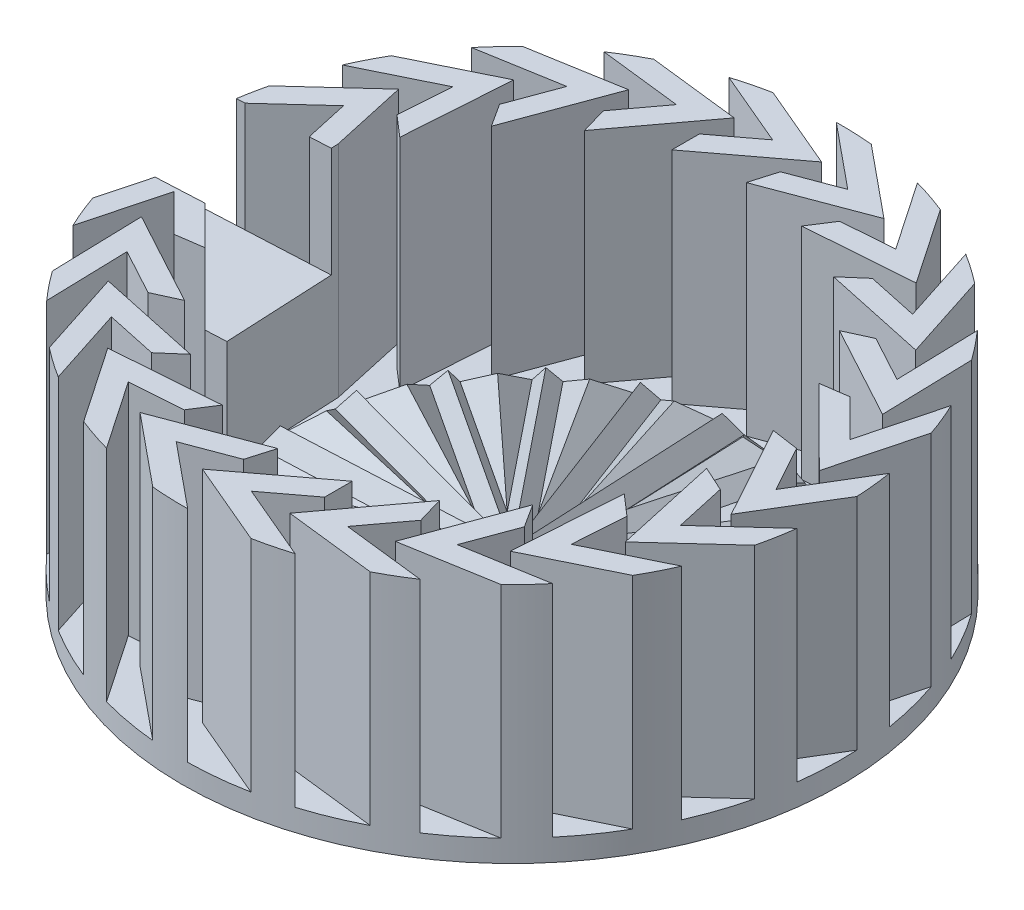
SolidWorks part; units mm, degrees
ref_plane "Front Plane" through (0, 0, 0) normal (0, 0, 1) x (1, 0, 0)
ref_plane "Top Plane" through (0, 0, 0) normal (0, 1, 0) x (1, 0, 0)
ref_plane "Right Plane" through (0, 0, 0) normal (1, 0, 0) x (0, 0, -1)
sketch "Sketch2" plane through (0, 0, 0) normal (0, 1, 0) x (1, 0, 0)
  circle A0 centre (0, 0) radius 30
  dimension "D1" = 60
extrude "Boss-Extrude1" add sketch "Sketch2" along normal blind 2
sketch "Sketch3" plane through (0, 2, 0) normal (0, 1, 0) x (1, 0, 0)
  line L0 (0, 0) -> (0, 30) construction
  line L1 (-7.364, 29.0821) -> (0, 25.9563) construction
  line L2 (0, 25.9563) -> (-6.3891, 21.1418) construction
  line L3 (-7.7548, 28.1616) -> (-1.9851, 25.7126) construction
  line L4 (-1.9851, 25.7126) -> (-6.9909, 21.9404) construction
  line L5 (-6.9733, 30.0026) -> (1.9851, 26.2) construction
  line L6 (1.9851, 26.2) -> (-5.7873, 20.3431) construction
  line L7 (-1.9851, 25.7126) -> (-8.9023, 28.6487)
  line L8 (1.9851, 26.2) -> (-5.686, 29.4562)
  line L11 (-5.7873, 20.3431) -> (1.9851, 26.2)
  line L12 (-1.9851, 25.7126) -> (-5.7873, 22.8474)
  line L13 (-5.7873, 22.8474) -> (-5.7873, 20.3431)
  circle A0 centre (0, 0) radius 30 construction
  arc A1 (-8.9023, 28.6487) -> (-5.686, 29.4562) centre (0, 0) cw
  dimension "D1" = 60
  dimension "D2" = 8
  dimension "D3" = 67
  dimension "D4" = 1
  dimension "D5" = 1
extrude "Boss-Extrude2" add sketch "Sketch3" along normal blind 20
pattern_circular "CirPattern1" count 22 over 360 about axis through (0, 2, 0) along (0, 1, 0) of "Boss-Extrude2"
sketch "Sketch5" plane through (0, 2, 0) normal (0, 1, 0) x (1, 0, 0)
  line L0 (0, 0) -> (11.5845, 17.6956) construction
  line L1 (0.8367, -0.5477) -> (12.4211, 17.1479)
  line L2 (-0.8367, 0.5477) -> (10.7478, 18.2434)
  line L3 (-0.8367, 0.5477) -> (0.8367, -0.5477)
  line L4 (10.7478, 18.2434) -> (12.4211, 17.1479)
  dimension "D1" = 1
  dimension "D2" = 1
extrude "Boss-Extrude4" add sketch "Sketch5" along normal blind 2 draft 30
pattern_circular "CirPattern2" count 20 over 360 about axis through (0, 2, 0) along (0, -1, 0) of "Boss-Extrude4" reverse direction yes
sketch "Sketch6" plane through (0, 2, 0) normal (0, 1, 0) x (1, 0, 0)
  line L0 (2.6215, 5.8302) -> (6.5142, 20.147)
  line L1 (6.5142, 20.147) -> (10.7478, 18.2434)
  line L2 (10.7478, 18.2434) -> (2.6215, 5.8302)
extrude "Boss-Extrude5" add sketch "Sketch6" along normal blind 2 draft 45
pattern_circular "CirPattern3" count 20 over 360 about axis through (0, 0, 0) along (0, 1, 0) of "Boss-Extrude5"
sketch "Sketch9" plane through (0, 22, 0) normal (0, 1, 0) x (1, 0, 0)
  line L5 (-25.7333, 1.6944) -> (-23.4385, -2.4768)
  line L6 (-23.4385, -2.4768) -> (-20.9597, -2.8332)
  line L7 (-20.9597, -2.8332) -> (-25.6508, 5.6935)
  line L8 (-25.6508, 5.6935) -> (-29.9656, -1.4361)
  line L9 (-29.624, -4.7345) -> (-25.7333, 1.6944)
  line L10 (-25.7333, 1.6944) -> (-23.4385, -2.4768)
  line L11 (-23.4385, -2.4768) -> (-20.9597, -2.8332)
  line L12 (-20.9597, -2.8332) -> (-25.6508, 5.6935)
  line L13 (-25.6508, 5.6935) -> (-29.9656, -1.4361)
  line L14 (-29.624, -4.7345) -> (-25.7333, 1.6944)
  arc A1 (-29.9656, -1.4361) -> (-29.624, -4.7345) centre (0, 0) ccw
  arc A2 (-29.9656, -1.4361) -> (-29.624, -4.7345) centre (0, 0) ccw
  dimension "D1" = 0
extrude "Cut-Extrude1" cut sketch "Sketch9" against normal blind 20
sketch "Sketch8" plane through (0, 2, 0) normal (0, 1, 0) x (1, 0, 0)
  line L0 (-21.1739, -0.0304) -> (-21.4172, 4.9637)
  line L1 (-21.4172, 4.9637) -> (-33.403, 4.3797)
  line L2 (-33.403, 4.3797) -> (-32.9164, -5.6084)
  line L3 (-32.9164, -5.6084) -> (-20.9306, -5.0245)
  line L4 (-20.9306, -5.0245) -> (-21.1739, -0.0304)
  line L5 (-6.3549, 0.6916) -> (-21.1739, -0.0304) construction
  dimension "D1" = 10
  dimension "D2" = 12
extrude "Boss-Extrude6" add sketch "Sketch8" along normal blind 20 and the other way blind 2
sketch "Sketch10" plane through (0, 22, 0) normal (0, 1, 0) x (1, 0, 0)
  line L3 (-20.9089, 3.1866) -> (-21.3402, 3.3836)
  line L4 (-20.9089, 3.1866) -> (-21.45, 5.6366)
  line L5 (-20.9089, 3.1866) -> (-23.0077, 12.6896) construction
  line L6 (-21.45, 5.6366) -> (-21.3402, 3.3836)
  line L7 (-20.9306, -5.0245) -> (-21.3402, 3.3836) construction
extrude "Cut-Extrude2" cut sketch "Sketch10" against normal blind 20
sketch "Sketch11" plane through (0, 22, 0) normal (0, 1, 0) x (1, 0, 0)
  line L0 (-33.403, 4.3797) -> (-32.9164, -5.6084)
  line L1 (-32.9164, -5.6084) -> (-20.9306, -5.0245)
  line L2 (-20.9306, -5.0245) -> (-21.4172, 4.9637)
  line L3 (-20.9306, -5.0245) -> (-21.45, 5.6366) construction
  line L4 (-21.4172, 4.9637) -> (-33.403, 4.3797)
extrude "Cut-Extrude3" cut sketch "Sketch11" against normal blind 10
